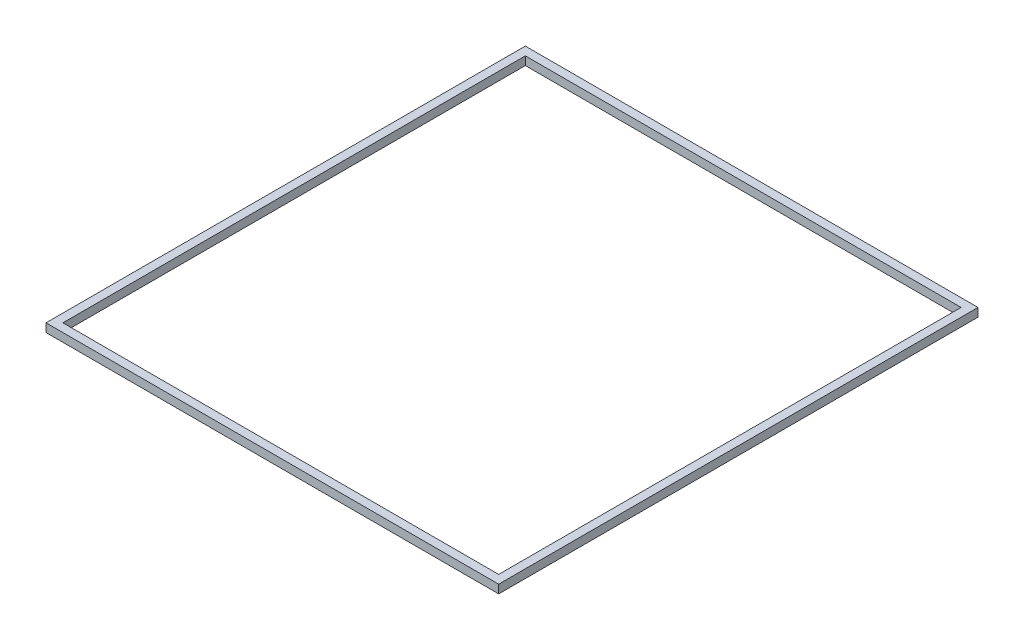
SolidWorks part; units mm, degrees
material "Silicon Rubber"
ref_plane "Front Plane" through (0, 0, 0) normal (0, 0, 1) x (1, 0, 0)
ref_plane "Top Plane" through (0, 0, 0) normal (0, 1, 0) x (1, 0, 0)
ref_plane "Right Plane" through (0, 0, 0) normal (1, 0, 0) x (0, 0, -1)
sketch "Sketch1" plane through (0, 0, 0) normal (0, 1, 0) x (1, 0, 0)
  line L1 (0, 0) -> (85, 0)
  line L2 (0, 0) -> (0, 90)
  line L3 (0, 90) -> (85, 90)
  line L4 (85, 0) -> (85, 90)
  line L5 (1.5875, 1.5875) -> (83.4125, 1.5875)
  line L6 (1.5875, 1.5875) -> (1.5875, 88.4125)
  line L7 (1.5875, 88.4125) -> (83.4125, 88.4125)
  line L8 (83.4125, 1.5875) -> (83.4125, 88.4125)
  dimension "D1" = 85
  dimension "D2" = 90
  dimension "D3" = 86.825
  dimension "D4" = 81.825
  dimension "D5" = 1.5875
  dimension "D6" = 1.5875
extrude "Boss-Extrude1" add sketch "Sketch1" along normal blind 1.5875
